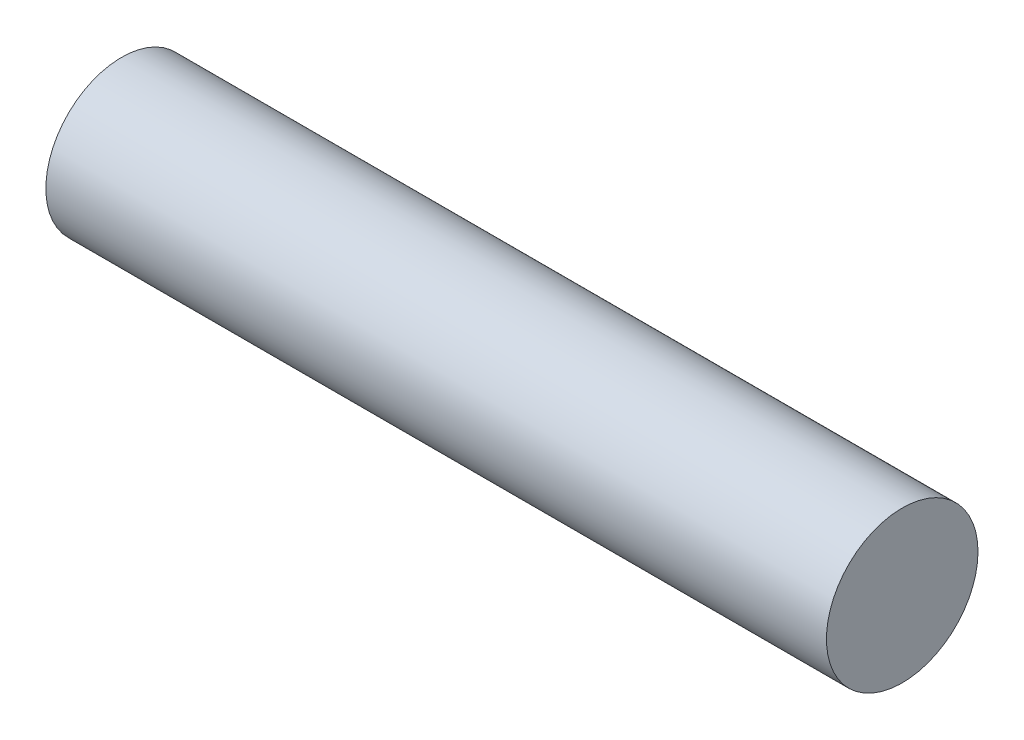
SolidWorks part; units mm, degrees
ref_plane "Front Plane" through (0, 0, 0) normal (0, 0, 1) x (1, 0, 0)
ref_plane "Top Plane" through (0, 0, 0) normal (0, 1, 0) x (1, 0, 0)
ref_plane "Right Plane" through (0, 0, 0) normal (1, 0, 0) x (0, 0, -1)
sketch "Sketch1" plane through (0, 0, 0) normal (0, 0, 1) x (1, 0, 0)
  line L0 (-62.0645, 19.05) -> (418.9847, 19.05) construction
  line L1 (-19.5631, 19.05) -> (376.6769, 19.05)
  line L2 (-19.5631, 19.05) -> (-19.5631, 0)
  line L3 (-19.5631, 0) -> (376.6769, 0)
  line L4 (376.6769, 19.05) -> (376.6769, 0)
revolve "Revolve1" add sketch "Sketch1" angle 360 about L0
sketch3d "3DSketch1"
  line L1 (125.1537, 38.1, 0) -> (125.1537, -7.0712, 0)
  line L2 (125.1537, -7.0712, 0) -> (-27.22, -7.0712, 0)
  line L3 (-27.22, -7.0712, 0) -> (-27.22, 54.7019, 0)
  line L4 (-27.22, 54.7019, 0) -> (126.9187, 54.7019, 0)
  line L6 (126.9187, 54.7019, 0) -> (125.1537, 38.1, 0)
extrude "Cut-Extrude1" cut sketch "3DSketch1" along direction (0, 0, 1) on the side against the normal blind 69.088 and the other way blind 101.6
sketch3d "3DSketch2"
  line L0 (376.6769, 19.05, 0) -> (125.1537, 19.05, 0) construction
  circle A0 centre (125.1537, 19.05, 0) radius 25.273
  point P2 (99.8807, 19.05, 0)
extrude "Boss-Extrude1" add sketch "3DSketch2" along direction (1, 0, 0) on the side of the normal blind 260.35
